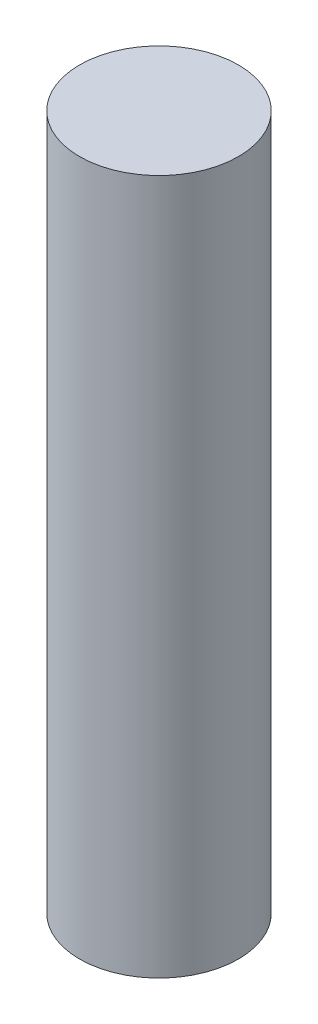
SolidWorks part; units mm, degrees
ref_plane "Front Plane" through (0, 0, 0) normal (0, 0, 1) x (1, 0, 0)
ref_plane "Top Plane" through (0, 0, 0) normal (0, 1, 0) x (1, 0, 0)
ref_plane "Right Plane" through (0, 0, 0) normal (1, 0, 0) x (0, 0, -1)
sketch "Sketch1" plane through (0, 0, 0) normal (0, 1, 0) x (1, 0, 0)
  circle A0 centre (0, 0) radius 4
  dimension "D1" = 8
extrude "Boss-Extrude1" add sketch "Sketch1" along normal blind 35
ref_plane "Plane2" through (0, 25, 0) normal (0, 1, 0) x (1, 0, 0)
ref_plane "Plane3" through (0, 17.5, 0) normal (0, 1, 0) x (1, 0, 0)
sketch "Sketch8" plane through (0, 25, 0) normal (0, 1, 0) x (1, 0, 0)
  circle A0 centre (0, 0) radius 5
ref_plane "Plane4" through (0, 10, 0) normal (0, -1, 0) x (-1, 0, 0)
sketch "Sketch9" plane through (0, 10, 0) normal (0, -1, 0) x (-1, 0, 0)
  circle A0 centre (0, 0) radius 5
